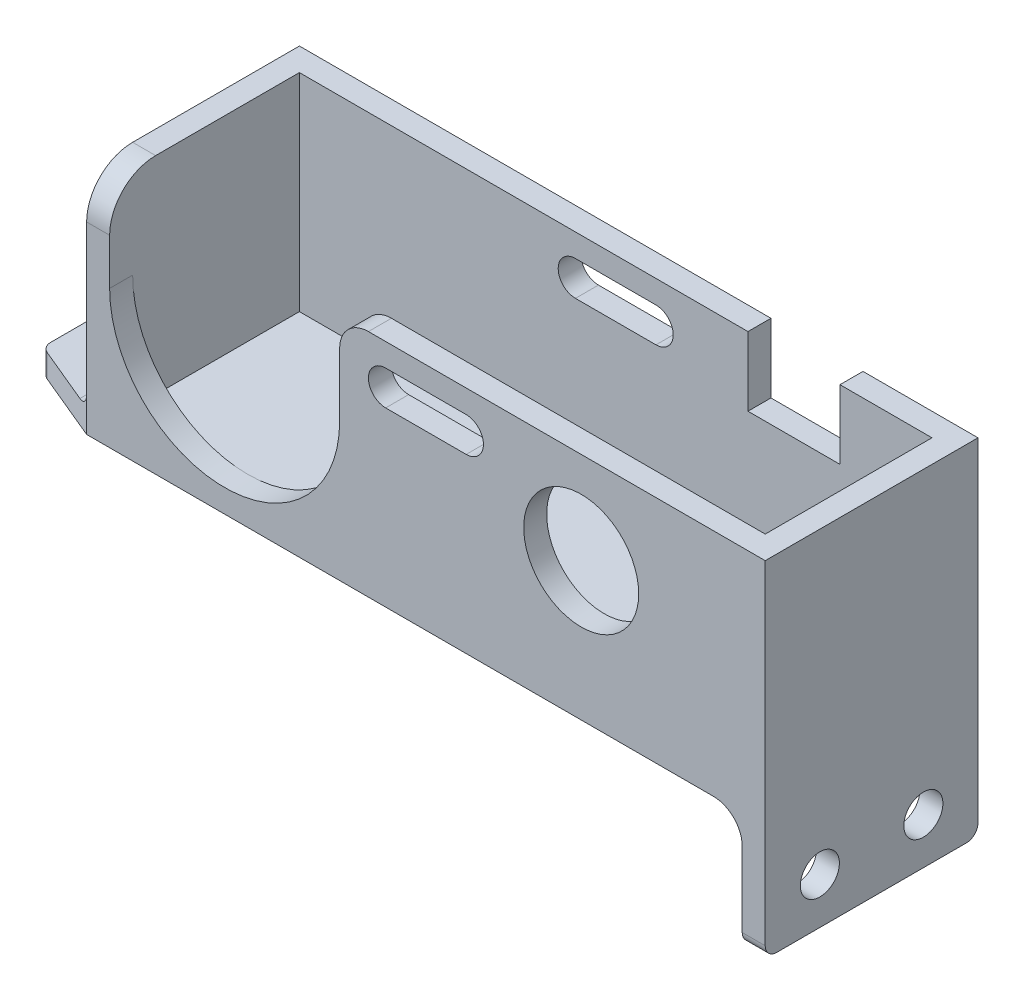
SolidWorks part; units mm, degrees
other "Markup1"
sketch "Sketch4" plane through (-28, -10, 6.5) normal (-0.9519, -0.1137, 0.2847) x (0.2678, 0.1434, 0.9527)
other "Markup2"
sketch "Sketch22" plane through (-36, 9, 9.25) normal (-0.1774, 0.9311, 0.3187) x (-0.0874, 0.3076, -0.9475)
ref_plane "Front Plane" through (0, 0, 0) normal (0, 0, 1) x (1, 0, 0)
ref_plane "Top Plane" through (0, 0, 0) normal (0, 1, 0) x (1, 0, 0)
ref_plane "Right Plane" through (0, 0, 0) normal (1, 0, 0) x (0, 0, -1)
sketch "Sketch1" plane through (0, 0, 0) normal (0, 0, 1) x (1, 0, 0)
  line L0 (-27.5, 0) -> (27.5, 0) construction
  line L1 (-27.5, 9) -> (27.5, 9)
  line L2 (-27.5, -9) -> (27.5, -9)
  line L5 (-27.5, 9) -> (-27.5, -9)
  line L6 (0, 9) -> (0, -9) construction
  line L8 (27.5, 9) -> (27.5, -9)
  point P2 (0, 0)
  dimension "D1" = 55
  dimension "D2" = 18
extrude "Boss-Extrude1" add sketch "Sketch1" along normal mid plane 14.5
shell "Shell2" thickness 2 removed face at (0, 9, 0) outward yes
sketch "Sketch11" plane through (0, 0, 9.25) normal (0, 0, 1) x (1, 0, 0)
  line L0 (-27.5, 9) -> (-27.5, 1)
  line L1 (29.5, 9) -> (-29.5, 9) construction
  line L2 (-7.5, 1) -> (-7.5, 9)
  line L3 (-27.5, 9) -> (-7.5, 9)
  line L4 (-27.5, -9) -> (27.5, -9) construction
  arc A0 (-27.5, 1) -> (-7.5, 1) centre (-17.5, 1) ccw
  dimension "D1" = 10
extrude "lens cutout" cut sketch "Sketch11" against normal up to next
sketch "Sketch12" plane through (0, 0, 9.25) normal (0, 0, 1) x (1, 0, 0)
  line L2 (13.5, 1) -> (-17.5, 1) construction
  circle A0 centre (13.5, 1) radius 5
  arc A1 (-27.5, 1) -> (-7.5, 1) centre (-17.5, 1) ccw construction
  dimension "D2" = 10
  dimension "D1" = 31
extrude "power button hole" cut sketch "Sketch12" against normal up to next
sketch "Sketch13" plane through (0, 0, -9.25) normal (0, 0, -1) x (-1, 0, 0)
  line L2 (-29.5, 9) -> (29.5, 9) construction
  line L3 (-19.5, 9) -> (-11.5, 9)
  line L4 (-19.5, 9) -> (-19.5, 3)
  line L5 (-19.5, 3) -> (-11.5, 3)
  line L6 (-11.5, 9) -> (-11.5, 3)
  arc A0 (7.5, 1) -> (17.5, -9) centre (17.5, 1) ccw construction
  point P0 (17.5, 1)
  dimension "D1" = 29
  dimension "D2" = 2
  dimension "D3" = 8
extrude "power cord cutout" cut sketch "Sketch13" against normal up to next
sketch "Sketch21" plane through (0, 0, 9.25) normal (0, 0, 1) x (1, 0, 0)
  line L0 (-3.5, 5.5) -> (3.5, 5.5) construction
  line L1 (-3.5, 7) -> (3.5, 7)
  line L2 (-3.5, 4) -> (3.5, 4)
  line L3 (29.5, 9) -> (-7.5, 9) construction
  arc A0 (-3.5, 7) -> (-3.5, 4) centre (-3.5, 5.5) ccw
  arc A1 (3.5, 4) -> (3.5, 7) centre (3.5, 5.5) ccw
  point P2 (0, 5.5)
  point P7 (-5, 5.5)
  dimension "D1" = 3
  dimension "D2" = 10
  dimension "D3" = 2
extrude "Cut-Extrude4" cut sketch "Sketch21" against normal through all
fillet "Fillet4" radius 2.5 1 edges at (-7.5, 9, 8.25)
sketch "Sketch15" plane through (0, -11, 0) normal (0, -1, 0) x (1, 0, 0)
  line L0 (-29.5, 9.25) -> (-29.5, -9.25)
  line L1 (-29.5, -9.25) -> (-36, -11.9646)
  line L2 (-36, -11.9646) -> (-36, 6.5354)
  line L3 (-36, 6.5354) -> (-29.5, 9.25)
  dimension "D1" = 67.333
  dimension "D2" = 6.5
extrude "Boss-Extrude3" add sketch "Sketch15" against normal blind 2
hole_wizard "M3 Clearance Hole1" positions "Sketch16" profile "Sketch17" hole size "M3" standard "ANSI Metric" end condition through all
sketch "Sketch16" plane through (0, -9, 0) normal (0, 1, 0) x (1, 0, 0)
  line L0 (-32.75, 10.6073) -> (-32.75, -7.8927) construction
  line L1 (-36, 11.9646) -> (-29.5, 9.25) construction
  line L2 (-29.5, -9.25) -> (-36, -6.5354) construction
  line L6 (-32.75, 1.3573) -> (-36, 1.3573) construction
  line L7 (-36, -6.5354) -> (-36, 11.9646) construction
  point P23 (-32.75, 1.3573)
sketch "Sketch17" plane through (-32.75, -9, -1.3573) normal (1, 0, 0) x (0, 0, 1)
  line L0 (0, 0) -> (0, 2)
  line L1 (0, 2) -> (1.7, 2)
  line L2 (1.7, 2) -> (1.7, 0)
  line L5 (1.7, 0) -> (0, 0)
  line L11 (0, -6.35) -> (0, 107.95) construction
  dimension "Thru Hole Dia." = 3.4
  dimension "Thru Hole Depth" = 2
fillet "Fillet2" radius 1 1 edges at (-29.5, -9, 0)
sketch "Sketch18" plane through (0, -11, 0) normal (0, -1, 0) x (1, 0, 0)
  line L0 (-29.5, -9.25) -> (29.5, -9.25) construction
  line L1 (29.5, 9.25) -> (27.5, 9.25)
  line L2 (29.5, 9.25) -> (29.5, -9.25)
  line L3 (29.5, -9.25) -> (27.5, -9.25)
  line L4 (27.5, 9.25) -> (27.5, -9.25)
  dimension "D1" = 2
extrude "Boss-Extrude4" add sketch "Sketch18" along normal blind 10
hole_wizard "M3 Clearance Hole2" positions "Sketch19" profile "Sketch20" hole size "M3" standard "ANSI Metric" end condition through all
sketch "Sketch19" plane through (27.5, 0, 0) normal (-1, 0, 0) x (0, 0, 1)
  line L0 (0, -21) -> (0, -11) construction
  line L1 (9.25, -21) -> (-9.25, -21) construction
  line L2 (9.25, -11) -> (-9.25, -11) construction
  point P0 (-4.5, -17)
  point P2 (4.5, -17)
  dimension "D1" = 9
  dimension "D2" = 4
sketch "Sketch20" plane through (27.5, -17, -4.5) normal (0, 1, 0) x (0, 0, 1)
  line L0 (0, 0) -> (0, 2)
  line L1 (0, 2) -> (1.7, 2)
  line L2 (1.7, 2) -> (1.7, 0)
  line L5 (1.7, 0) -> (0, 0)
  line L11 (0, -6.35) -> (0, 107.95) construction
  dimension "Thru Hole Dia." = 3.4
  dimension "Thru Hole Depth" = 2
fillet "Fillet3" radius 2.5 1 edges at (27.5, -11, 0)
fillet "Fillet5" radius 4 1 edges at (-28.5, 9, 9.25)
fillet "Fillet6" radius 1 4 edges at (28.5, -21, -9.25) (28.5, -21, 9.25) (-36, -10, -11.9646) (-36, -10, 6.5354)
equation "\"wallthickness\"= 2"
equation "\"D1@Shell2\"=\"wallthickness\""
equation "\"D1@Boss-Extrude3\"=\"wallthickness\""
equation "\"D1@Sketch18\"=\"wallthickness\""
